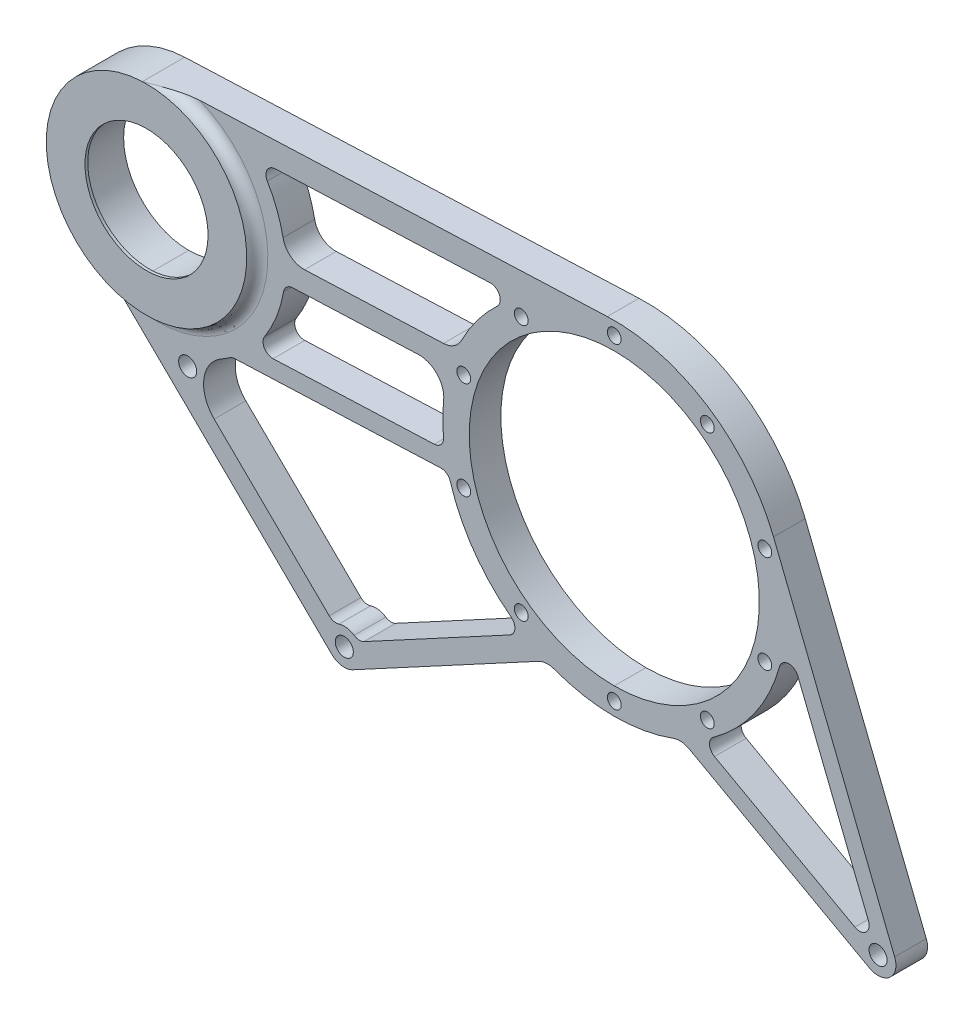
SolidWorks part; units mm, degrees
material "6061-T6 (SS)"
ref_plane "Front Plane" through (0, 0, 0) normal (0, 0, 1) x (1, 0, 0)
ref_plane "Top Plane" through (0, 0, 0) normal (0, 1, 0) x (1, 0, 0)
ref_plane "Right Plane" through (0, 0, 0) normal (1, 0, 0) x (0, 0, -1)
sketch "Sketch1" plane through (0, 0, 0) normal (0, 0, 1) x (1, 0, 0)
  line L0 (-114.3, 95.25) -> (-114.3, 107.95) construction
  line L1 (-280.8642, 163.1704) -> (-116.8043, 169.8118)
  line L2 (-304.7421, 101.1501) -> (-216.3071, 14.4521)
  line L3 (-13.0706, 21.4387) -> (-56.8054, 130.918)
  line L4 (-208.742, 13.3833) -> (-141.7118, 49.5504)
  line L5 (-22.1639, 13.4141) -> (-87.2342, 49.3665)
  circle A0 centre (-279.4, 127) radius 23.5
  circle A1 centre (-114.3, 95.25) radius 36 construction
  circle A2 centre (0, 0) radius 12.7 construction
  circle A3 centre (-228.6, 0) radius 12.7 construction
  circle A4 centre (-114.3, 107.95) radius 52.3875
  circle A5 centre (-19.05, 19.05) radius 3.2639
  circle A6 centre (-211.7995, 19.05) radius 3.2639
  circle A7 centre (-279.4, 127) radius 36.2
  arc A8 (-135.9521, 49.947) -> (-93.0137, 49.8118) centre (-114.3, 107.95) ccw
  arc A9 (-216.3071, 14.4521) -> (-208.742, 13.3833) centre (-211.7995, 19.05) ccw
  arc A10 (-22.1639, 13.4141) -> (-13.0706, 21.4387) centre (-19.05, 19.05) ccw
  arc A11 (-56.8054, 130.918) -> (-116.8043, 169.8118) centre (-114.3, 107.95) ccw
  arc A12 (-135.9521, 49.947) -> (-141.7118, 49.5504) centre (-138.3949, 43.4031) ccw
  arc A13 (-87.2342, 49.3665) -> (-93.0137, 49.8118) centre (-90.6122, 43.2526) ccw
  dimension "D5" = 72
  dimension "D6" = 47
  dimension "D7" = 25.4
  dimension "D8" = 25.4
  dimension "D11" = 104.775
  dimension "D14" = 6.5278
  dimension "D15" = 6.5278
  dimension "D16" = 25.4
  dimension "D17" = 12.7
  dimension "D18" = 123.825
  dimension "D19" = 3.175
  dimension "D20" = 6.985
  dimension "D21" = 6.985
  dimension "D1" = 114.3
  dimension "D2" = 95.25
  dimension "D3" = 279.4
  dimension "D4" = 127
  dimension "D9" = 228.6
  dimension "D10" = 12.7
  dimension "D12" = 19.05
  dimension "D13" = 19.05
extrude "Boss-Extrude1" add sketch "Sketch1" along normal blind 11.43 contours A13 L5 A10 L3 A11 L1 A7 L2 A9 L4 A12 A8 A6 A5 A4 | A7 A0 region at (-168.693, 91.0379, 0) region at (-255.035, 152.3713, 0)
sketch "Sketch2" plane through (0, 0, 11.43) normal (0, 0, 1) x (1, 0, 0)
  circle A0 centre (-279.4, 127) radius 36.2
  circle A1 centre (-279.4, 127) radius 23.5
extrude "Boss-Extrude2" add sketch "Sketch2" along normal blind 3.81
fillet "Fillet1" radius 3.81 1 edges at (-245.6173, 113.9936, 11.43)
sketch "Sketch3" plane through (0, 0, 11.43) normal (0, 0, 1) x (1, 0, 0)
  line L0 (-114.3, 107.95) -> (-114.3, 165.1) construction
  circle A0 centre (-114.3, 107.95) radius 57.15 construction
  circle A1 centre (-114.3, 165.1) radius 2.5
  circle A2 centre (-80.7081, 154.1853) radius 2.5
  circle A3 centre (-59.9471, 125.6103) radius 2.5
  circle A4 centre (-59.9471, 90.2897) radius 2.5
  circle A5 centre (-80.7081, 61.7147) radius 2.5
  circle A6 centre (-114.3, 50.8) radius 2.5
  circle A7 centre (-147.8919, 61.7147) radius 2.5
  circle A8 centre (-168.6529, 90.2897) radius 2.5
  circle A9 centre (-168.6529, 125.6103) radius 2.5
  circle A10 centre (-147.8919, 154.1853) radius 2.5
  point P25 (-114.3, 107.95)
  dimension "D1" = 114.3
  dimension "D2" = 5
  dimension "D3" = 10
extrude "5mm Holes" cut sketch "Sketch3" against normal through all
sketch "Sketch4" plane through (0, 0, 15.24) normal (0, 0, 1) x (1, 0, 0)
  circle A0 centre (-279.4, 127) radius 22.225
  circle A1 centre (-279.4, 127) radius 23.5 construction
  circle A2 centre (-279.4, 127) radius 23.5
  dimension "D1" = 44.45
extrude "Boss-Extrude3" add sketch "Sketch4" against normal blind 1
sketch "Sketch5" plane through (0, 0, 11.43) normal (0, 0, 1) x (1, 0, 0)
  line L0 (-48.0193, 91.8071) -> (-22.5033, 27.9342)
  line L1 (-13.0706, 21.4387) -> (-56.8054, 130.918) construction
  line L2 (-78.1047, 51.5771) -> (-27.4356, 23.5816)
  line L3 (-22.1639, 13.4141) -> (-87.2342, 49.3665) construction
  line L4 (-236.7455, 156.0591) -> (-159.125, 159.2013)
  line L5 (-263.8382, 163.8596) -> (-116.8043, 169.8118) construction
  line L6 (-226.1253, 129.7972) -> (-175.9845, 131.827)
  line L7 (-230.4174, 121.9972) -> (-185.1154, 123.8311)
  line L8 (-258.7869, 66.7686) -> (-217.2302, 26.028)
  line L9 (-204.6483, 24.2506) -> (-152.0143, 52.6499)
  line L10 (-292.5742, 89.2212) -> (-216.3071, 14.4521) construction
  line L11 (-208.742, 13.3833) -> (-141.7118, 49.5504) construction
  line L12 (-237.4937, 96.2899) -> (-179.3047, 98.6455)
  line L13 (-251.3498, 89.3738) -> (-177.0086, 92.3833)
  arc A0 (-175.0426, 119.9291) -> (-175.9673, 102.4457) centre (-114.3, 107.95) ccw construction
  circle A1 centre (-211.7995, 19.05) radius 6.4389 construction
  circle A2 centre (-19.05, 19.05) radius 6.4389 construction
  arc A3 (-54.6287, 91.4427) -> (-78.4387, 57.481) centre (-114.3, 107.95) cw
  arc A4 (-48.0193, 91.8071) -> (-54.6287, 91.4427) centre (-51.2626, 90.5115) ccw
  arc A5 (-27.4356, 23.5816) -> (-22.5033, 27.9342) centre (-25.7466, 26.6385) ccw
  arc A6 (-78.1047, 51.5771) -> (-78.4387, 57.481) centre (-76.4157, 54.634) cw
  arc A7 (-233.9104, 135.9413) -> (-239.6024, 150.7781) centre (-279.4, 127) ccw construction
  arc A8 (-292.5742, 89.2212) -> (-263.8382, 163.8596) centre (-279.4, 127) ccw construction
  arc A9 (-213.7352, 25.191) -> (-208.2383, 24.4145) centre (-211.7995, 19.05) cw
  arc A10 (-156.5977, 153.1613) -> (-169.499, 135.9897) centre (-114.3, 107.95) ccw
  arc A11 (-175.9093, 114.0697) -> (-175.9673, 102.4457) centre (-114.3, 107.95) ccw
  arc A12 (-173.5263, 89.9112) -> (-151.5703, 58.5123) centre (-114.3, 107.95) ccw
  arc A13 (-239.6024, 150.7781) -> (-233.9104, 135.9413) centre (-279.4, 127) cw
  arc A14 (-233.7176, 119.1025) -> (-240.5609, 101.6865) centre (-279.4, 127) cw
  arc A15 (-240.5609, 101.6865) -> (-233.7176, 119.1025) centre (-279.4, 127) ccw construction
  arc A16 (-253.1835, 88.7646) -> (-256.2406, 86.8392) centre (-279.4, 127) cw
  arc A17 (-159.125, 159.2013) -> (-156.5977, 153.1613) centre (-158.9837, 155.7117) cw
  arc A20 (-236.7455, 156.0591) -> (-239.6024, 150.7781) centre (-236.6043, 152.5695) ccw
  arc A21 (-179.3047, 98.6455) -> (-175.9673, 102.4457) centre (-179.446, 102.1352) ccw
  arc A23 (-230.4174, 121.9972) -> (-233.7176, 119.1025) centre (-230.2762, 118.5075) ccw
  arc A24 (-237.4937, 96.2899) -> (-240.5609, 101.6865) centre (-237.6349, 99.7796) cw
  arc A25 (-217.2302, 26.028) -> (-213.7352, 25.191) centre (-214.7852, 28.522) ccw
  arc A26 (-204.6483, 24.2506) -> (-208.2383, 24.4145) centre (-206.3067, 27.3242) cw
  arc A27 (-152.0143, 52.6499) -> (-151.5703, 58.5123) centre (-153.6727, 55.7236) ccw
  arc A28 (-177.0086, 92.3833) -> (-173.5263, 89.9112) centre (-176.8673, 88.8936) cw
  arc A29 (-251.3498, 89.3738) -> (-253.1835, 88.7646) centre (-251.2085, 85.8842) ccw
  arc A31 (-173.5263, 89.9112) -> (-170.4887, 133.9499) centre (-114.3, 107.95) ccw construction
  arc A32 (-273.3418, 81.0375) -> (-253.1835, 88.7646) centre (-279.4, 127) ccw construction
  arc A33 (-258.7869, 66.7686) -> (-256.2406, 86.8392) centre (-249.8962, 75.8374) cw
  arc A34 (-169.499, 135.9897) -> (-175.9845, 131.827) centre (-176.2928, 139.4407) cw
  arc A35 (-233.9104, 135.9413) -> (-226.1253, 129.7972) centre (-226.4335, 137.411) ccw
  arc A36 (-185.1154, 123.8311) -> (-175.9093, 114.0697) centre (-184.7558, 114.9484) cw
  point P17 (-52.5701, 103.1988)
  point P23 (-83.2204, 54.4036)
  point P51 (-148.3837, 159.6362)
  point P54 (-171.3442, 132.0148)
  point P60 (-243.0732, 155.8029)
  point P63 (-175.5324, 98.7982)
  point P66 (-174.02, 124.2803)
  point P75 (-215.4925, 24.3245)
  point P78 (-206.7898, 23.0951)
  point P81 (-146.981, 55.3657)
  point P84 (-174.2524, 92.4948)
  point P90 (-273.3418, 81.0375)
  dimension "D1" = 123.825
  dimension "D2" = 12.8778
  dimension "D5" = 3.4925
  dimension "D6" = 6.35
  dimension "D14" = 3.4925
  dimension "D15" = 12.7
  dimension "D16" = 7.62
  dimension "D17" = 7.62
  dimension "D18" = 8.89
  dimension "D3" = 6.35
  dimension "D4" = 6.35
  dimension "D7" = 8.89
  dimension "D8" = 7.62
  dimension "D9" = 7.62
  dimension "D10" = 7.62
  dimension "D11" = 6.35
  dimension "D12" = 25.4
  dimension "D13" = 26.67
extrude "Cut-Extrude2" cut sketch "Sketch5" against normal through all both and the other way through all
ref_axis "Axis2" through (-279.4, 127, 14.24) along (0, 0, -1)
ref_axis "Axis1" through (-114.3, 107.95, 11.43) along (0, 0, -1)
ref_plane "Plane1" through (-114.3, 0, 0) normal (1, 0, 0) x (0, 0, -1)
ref_plane "Plane2" through (-279.4, 0, 0) normal (1, 0, 0) x (0, 0, -1)
ref_plane "Plane3" through (0, 0, 5.715) normal (0, 0, -1) x (-1, 0, 0)
ref_plane "Plane4" through (0, 0, 7.12) normal (0, 0, -1) x (-1, 0, 0)
split line "Split Line1"
split line "Split Line2"
sketch "Sketch6" plane through (0, 0, 5.715) normal (0, 0, -1) x (-1, 0, 0)
  circle A1 centre (114.3, 107.95) radius 52.3875 construction
sketch "Sketch7" plane through (0, 0, 7.12) normal (0, 0, -1) x (-1, 0, 0)
  circle A0 centre (279.4, 127) radius 23.5
sketch "Sketch8" plane through (0, 0, 11.43) normal (0, 0, 1) x (1, 0, 0)
  circle A0 centre (-268.3542, 78.4783) radius 3.2639
extrude "Cut-Extrude3" cut sketch "Sketch8" against normal through all both and the other way through all
